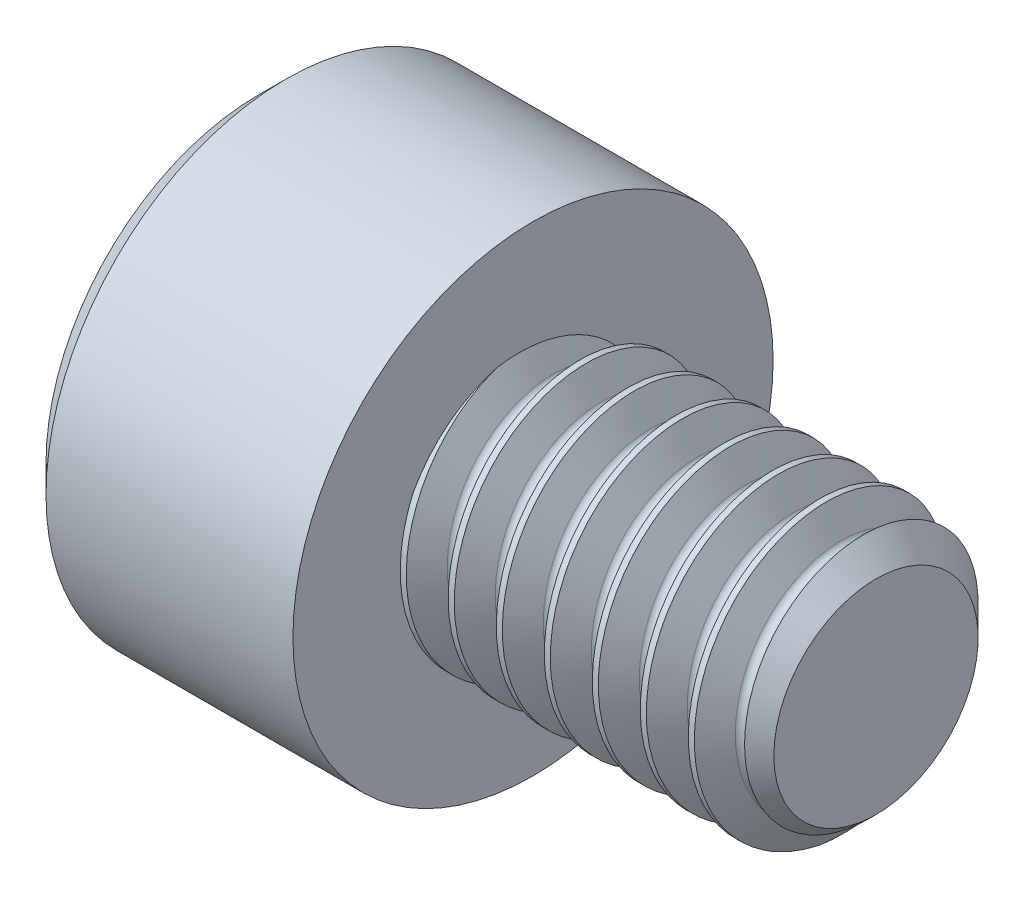
SolidWorks part; units mm, degrees
material "AISI Type 316L stainless steel"
ref_plane "Front Plane" through (0, 0, 0) normal (0, 0, 1) x (1, 0, 0)
ref_plane "Top Plane" through (0, 0, 0) normal (0, 1, 0) x (1, 0, 0)
ref_plane "Right Plane" through (0, 0, 0) normal (1, 0, 0) x (0, 0, -1)
sketch "Sketch1" plane through (0, 0, 0) normal (0, 0, 1) x (1, 0, 0)
  line L0 (-88.7055, 0) -> (96.9812, 0) construction
  line L1 (0, 0) -> (0, 3.5)
  line L2 (0, 3.5) -> (4, 3.5)
  line L4 (9, 0) -> (9, 1.989)
  line L5 (9, 1.989) -> (4, 1.989)
  line L6 (4, 1.989) -> (4, 3.5)
  line L7 (0, 0) -> (9, 0)
revolve "Revolve1" add sketch "Sketch1" angle 360 about L0
chamfer "Chamfer1" distance 0.5 angle 45 1 edges at (9, 0, 1.989)
chamfer "Chamfer2" distance 0.4 angle 45 1 edges at (0, 0, 3.5)
sketch "Sketch3" plane through (0, 0, 0) normal (1, 0, 0) x (0, 0, -1)
  line L1 (-1.7321, 0) -> (-0.866, -1.5)
  line L2 (-0.866, -1.5) -> (0.866, -1.5)
  line L3 (0.866, -1.5) -> (1.7321, 0)
  line L4 (1.7321, 0) -> (0.866, 1.5)
  line L5 (0.866, 1.5) -> (-0.866, 1.5)
  line L6 (-0.866, 1.5) -> (-1.7321, 0)
  circle A0 centre (0, 0) radius 1.5 construction
extrude "Cut-Extrude1" cut sketch "Sketch3" along normal blind 2
chamfer "Chamfer3" distance 0.3 angle 45 6 edges at (0, 1.5, 0) (0, 0.75, 1.299) (0, -0.75, 1.299) (0, -1.5, 0) (0, -0.75, -1.299) (0, 0.75, -1.299)
sketch "Sketch5" plane through (9, 0, 0) normal (1, 0, 0) x (0, 0, -1)
  circle A0 centre (0, 0) radius 1.989
curve "Helix/Spiral1" pitch 0.7 height 5 radius 1.989 centre (9, 0, 0) axis (-1, 0, 0) start towards (0, 0, -1)
sketch "Sketch8" plane through (0, 0, 0) normal (0, 1, 0) x (1, 0, 0)
  line L0 (9, 1.989) -> (9, 1.4588) construction
  line L1 (9.0875, 1.6102) -> (9.4592, 2.2541)
  line L2 (9.4592, 2.2541) -> (8.5408, 2.2541)
  line L3 (8.5408, 2.2541) -> (8.9125, 1.6102)
  line L4 (9, -1.489) -> (9, 1.489) construction
  circle A0 centre (9, 1.989) radius 0.2651 construction
  arc A1 (9.0875, 1.6102) -> (8.9125, 1.6102) centre (9, 1.6607) cw
  dimension "D2" = 0.101
  dimension "D1" = 0.5302
sweep "Cut-Sweep1" cut profiles "Sketch8" path "Helix/Spiral1" align with end faces yes
